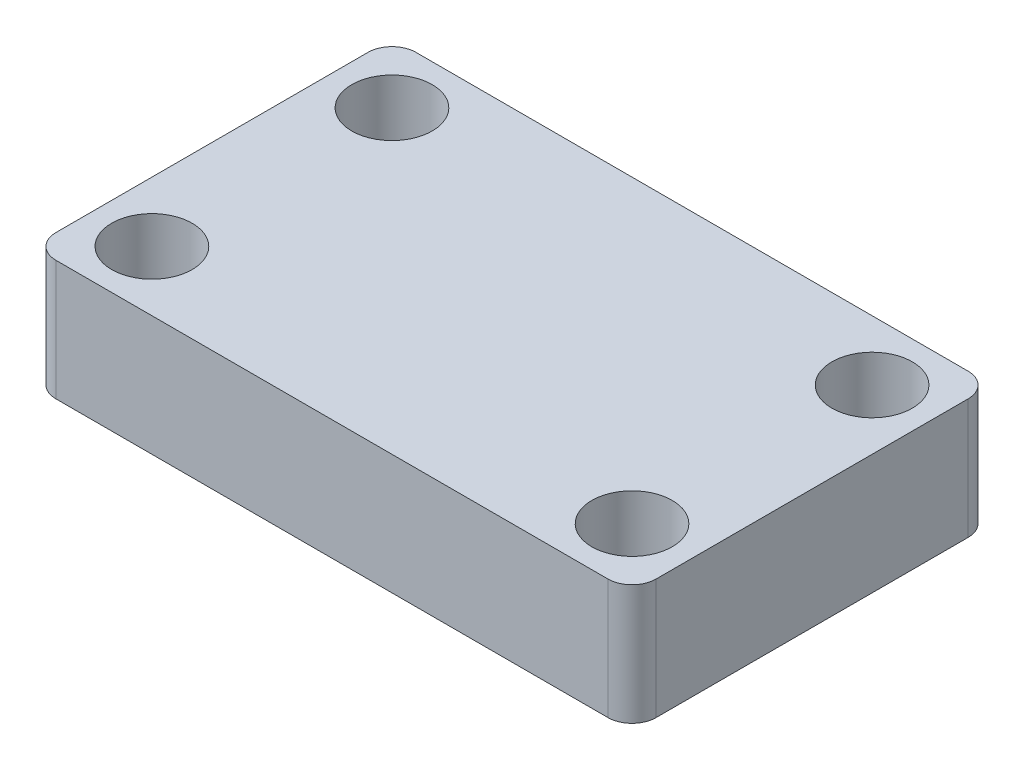
SolidWorks part; units mm, degrees
ref_plane "Front Plane" through (0, 0, 0) normal (0, 0, 1) x (1, 0, 0)
ref_plane "Top Plane" through (0, 0, 0) normal (0, 1, 0) x (1, 0, 0)
ref_plane "Right Plane" through (0, 0, 0) normal (1, 0, 0) x (0, 0, -1)
sketch "Sketch1" plane through (0, 0, 0) normal (0, 1, 0) x (1, 0, 0)
  line L0 (0, 0) -> (-20, 0) construction
  line L1 (-25, 15) -> (25, 15)
  line L2 (-25, 15) -> (-25, -15)
  line L3 (-25, -15) -> (25, -15)
  line L4 (25, 15) -> (25, -15)
  line L5 (-25, 15) -> (25, -15) construction
  line L6 (-25, -15) -> (25, 15) construction
  line L7 (-20, 0) -> (-20, 10) construction
  line L8 (-20, 10) -> (20, 10) construction
  line L9 (20, 10) -> (20, -10) construction
  line L10 (20, -10) -> (-20, -10) construction
  circle A0 centre (-20, 10) radius 3.35
  circle A1 centre (20, 10) radius 3.35
  circle A2 centre (-20, -10) radius 3.35
  circle A3 centre (20, -10) radius 3.35
  point P0 (0, 0)
extrude "Boss-Extrude2" add sketch "Sketch1" along normal blind 10
sketch "Sketch10" plane through (0, 0, -15) normal (0, 0, -1) x (-1, 0, 0)
  line L0 (-25, 10) -> (25, 0) construction
  line L1 (25, 0) -> (0, 5) construction
hole_wizard "#8-32 Tapped Hole3" positions "3DSketch2" profile "Sketch11" tap size "#8-32" standard "ANSI Inch"
sketch3d "3DSketch2"
  point P0 (0, 5, -15)
sketch "Sketch11" plane through (0, 5, -15) normal (1, 0, 0) x (0, 1, 0)
  line L0 (0, 0) -> (0, 6.0378)
  line L1 (0, 6.0378) -> (1.7272, 5)
  line L2 (1.7272, 5) -> (1.7272, 0)
  line L5 (1.7272, 0) -> (0, 0)
  line L10 (0, 6.0378) -> (-1.7272, 5) construction
  line L11 (0, -6.35) -> (0, 107.95) construction
  dimension "Tap Drill Dia." = 3.4544
  dimension "Tap Drill Depth" = 5
  dimension "Drill Angle" = 118
cosmetic thread "Hole Thread3" parameters "D1"=4, "D2"=4.1656
fillet "Fillet3" radius 2 3 edges at (-25, 5, -15) (25, 5, 15) (25, 5, -15)
fillet "Fillet4" radius 2 1 edges at (-25, 5, 15)
